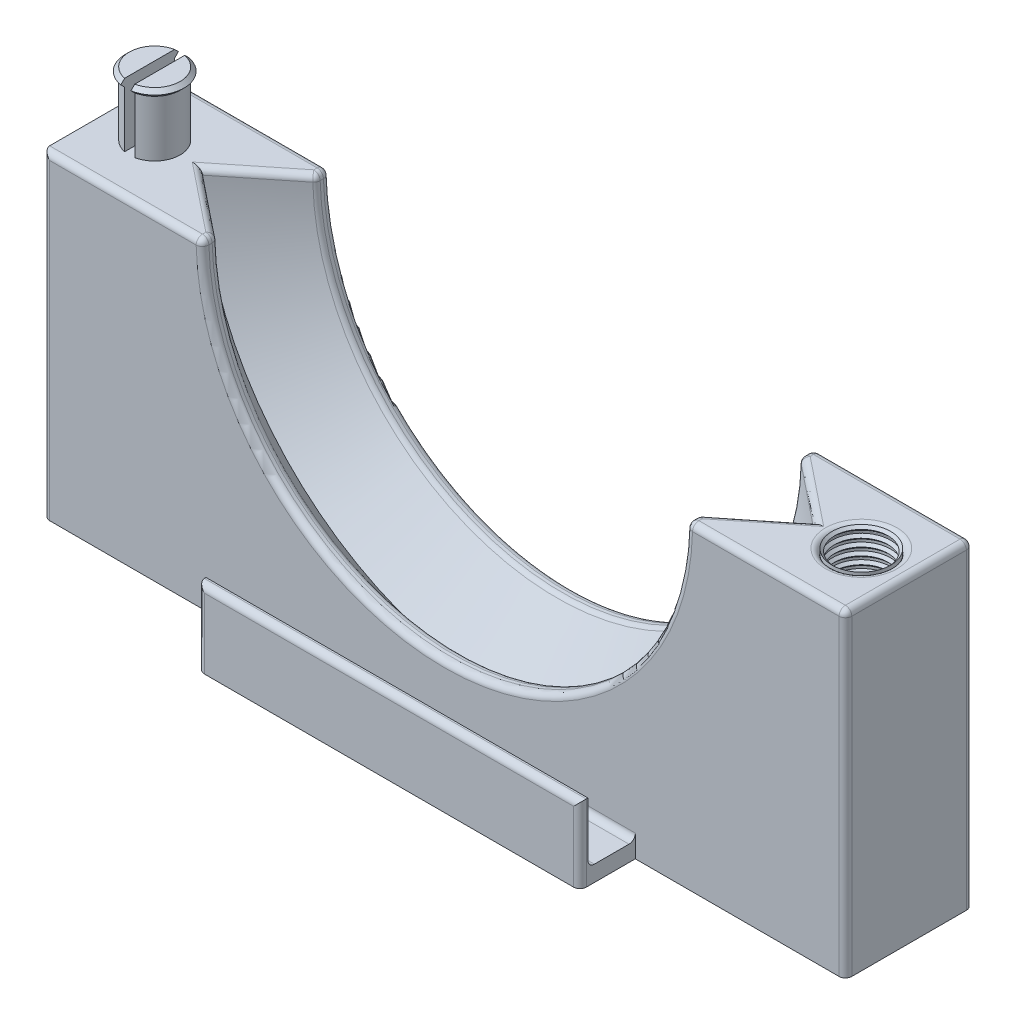
SolidWorks part; units mm, degrees
ref_plane "Front Plane" through (0, 0, 0) normal (0, 0, 1) x (1, 0, 0)
ref_plane "Top Plane" through (0, 0, 0) normal (0, 1, 0) x (1, 0, 0)
ref_plane "Right Plane" through (0, 0, 0) normal (1, 0, 0) x (0, 0, -1)
sketch "Sketch1" plane through (0, 0, 0) normal (0, 0, 1) x (1, 0, 0)
  line L0 (-40.005, 0) -> (40.005, 0)
  line L1 (40.005, 0) -> (40.005, 31.75)
  line L2 (40.005, 31.75) -> (24.13, 31.75)
  line L3 (-24.13, 31.75) -> (-40.005, 31.75)
  line L4 (-40.005, 31.75) -> (-40.005, 0)
  arc A0 (24.13, 31.75) -> (-24.13, 31.75) centre (0, 31.75) cw
  point P7 (0, 0)
  dimension "D2" = 24.13
  dimension "D1" = 31.75
  dimension "D3" = 15.875
extrude "Boss-Extrude1" add sketch "Sketch1" along normal blind 12.7
sketch "Sketch2" plane through (0, 31.75, 0) normal (0, 1, 0) x (1, 0, 0)
  line L0 (24.13, -11.43) -> (30.48, -6.35)
  line L2 (24.13, -12.7) -> (24.13, 0) construction
  line L3 (30.48, -6.35) -> (24.13, -1.27)
  line L4 (22.8654, -6.35) -> (40.005, -6.35) construction
  line L5 (24.13, -1.27) -> (24.13, -11.43)
  line L6 (40.005, -12.7) -> (40.005, 0) construction
  line L7 (0, 0) -> (0, -23.6383) construction
  dimension "D1" = 10.16
  dimension "D2" = 6.35
revolve "Cut-Revolve1" cut sketch "Sketch2" angle 360 about L7
sketch "Sketch6" plane through (0, 31.75, 0) normal (0, 1, 0) x (1, 0, 0)
  line L0 (30.48, -6.35) -> (40.005, -6.35) construction
  line L1 (40.005, -12.7) -> (40.005, 0) construction
  circle A0 centre (35.2425, -6.35) radius 2.921
  dimension "D1" = 5.842
extrude "Cut-Extrude2" cut sketch "Sketch6" against normal blind 9.525
sketch "Sketch11" plane through (0, 31.75, 0) normal (0, 1, 0) x (1, 0, 0)
  line L0 (30.48, -6.35) -> (40.005, -6.35) construction
  line L1 (40.005, -12.7) -> (40.005, 0) construction
ref_plane "Plane1" through (0, 0, 6.35) normal (0, 0, 1) x (1, 0, 0)
sketch "Sketch15" plane through (0, 0, 6.35) normal (0, 0, 1) x (1, 0, 0)
  line L0 (-37.7825, 31.75) -> (-37.7825, 37.338)
  line L1 (-24.13, 31.75) -> (-40.005, 31.75) construction
  line L2 (-37.7825, 37.338) -> (-38.1635, 37.719)
  line L3 (-38.1635, 37.719) -> (-37.7825, 38.1)
  line L4 (-37.7825, 38.1) -> (-35.2425, 38.1)
  line L5 (-35.2425, 38.1) -> (-35.2425, 31.75)
  line L6 (-35.2425, 31.75) -> (-37.7825, 31.75)
  line L7 (-40.005, 31.75) -> (-40.005, 0) construction
  line L8 (-37.7825, 38.1) -> (-37.7825, 37.338) construction
  line L9 (-30.48, 31.75) -> (-40.005, 31.75) construction
  dimension "D1" = 2.54
  dimension "D3" = 6.35
  dimension "D4" = 90
  dimension "D5" = 2.921
revolve "Revolve2" add sketch "Sketch15" angle 360 about L5
sketch "Sketch12" plane through (0, 0, 6.35) normal (0, 0, 1) x (1, 0, 0)
  line L0 (35.2425, 31.75) -> (35.2425, 26.6144) construction
  line L1 (30.48, 31.75) -> (40.005, 31.75) construction
  line L2 (32.3215, 30.48) -> (32.5755, 30.734)
  line L3 (32.3215, 31.242) -> (32.5755, 31.496)
  line L4 (32.5755, 31.496) -> (32.3215, 31.75)
  line L5 (32.3215, 31.75) -> (32.3215, 31.242)
  line L6 (35.2425, 31.75) -> (32.3215, 31.75) construction
  line L7 (32.5755, 30.734) -> (32.3215, 30.988)
  line L8 (32.3215, 30.988) -> (32.3215, 30.48)
  line L9 (32.3215, 29.718) -> (32.5755, 29.972)
  line L10 (32.5755, 29.972) -> (32.3215, 30.226)
  line L11 (32.3215, 30.226) -> (32.3215, 29.718)
  line L12 (32.3215, 28.956) -> (32.5755, 29.21)
  line L13 (32.5755, 29.21) -> (32.3215, 29.464)
  line L14 (32.3215, 29.464) -> (32.3215, 28.956)
  line L15 (32.3215, 28.194) -> (32.5755, 28.448)
  line L16 (32.5755, 28.448) -> (32.3215, 28.702)
  line L17 (32.3215, 28.702) -> (32.3215, 28.194)
  line L18 (32.3215, 27.432) -> (32.5755, 27.686)
  line L19 (32.5755, 27.686) -> (32.3215, 27.94)
  line L20 (32.3215, 27.94) -> (32.3215, 27.432)
  line L21 (32.3215, 26.67) -> (32.5755, 26.924)
  line L22 (32.5755, 26.924) -> (32.3215, 27.178)
  line L23 (32.3215, 27.178) -> (32.3215, 26.67)
  line L24 (32.3215, 25.908) -> (32.5755, 26.162)
  line L25 (32.5755, 26.162) -> (32.3215, 26.416)
  line L26 (32.3215, 26.416) -> (32.3215, 25.908)
  line L27 (32.3215, 25.146) -> (32.5755, 25.4)
  line L28 (32.5755, 25.4) -> (32.3215, 25.654)
  line L29 (32.3215, 25.654) -> (32.3215, 25.146)
  line L30 (32.3215, 24.384) -> (32.5755, 24.638)
  line L31 (32.5755, 24.638) -> (32.3215, 24.892)
  line L32 (32.3215, 24.892) -> (32.3215, 24.384)
  line L33 (32.3215, 23.622) -> (32.5755, 23.876)
  line L34 (32.5755, 23.876) -> (32.3215, 24.13)
  line L35 (32.3215, 24.13) -> (32.3215, 23.622)
  line L36 (32.3215, 22.86) -> (32.5755, 23.114)
  line L37 (32.5755, 23.114) -> (32.3215, 23.368)
  line L38 (32.3215, 23.368) -> (32.3215, 22.86)
  line L39 (32.3215, 22.098) -> (32.5755, 22.352)
  line L40 (32.5755, 22.352) -> (32.3215, 22.606)
  line L41 (32.3215, 22.606) -> (32.3215, 22.098)
  line L42 (32.3215, 21.336) -> (32.5755, 21.59)
  line L43 (32.5755, 21.59) -> (32.3215, 21.844)
  line L44 (32.3215, 21.844) -> (32.3215, 21.336)
  line L45 (32.3215, 20.574) -> (32.5755, 20.828)
  line L46 (32.5755, 20.828) -> (32.3215, 21.082)
  line L47 (32.3215, 21.082) -> (32.3215, 20.574)
  line L48 (32.3215, 19.812) -> (32.5755, 20.066)
  line L49 (32.5755, 20.066) -> (32.3215, 20.32)
  line L50 (32.3215, 20.32) -> (32.3215, 19.812)
  line L51 (32.3215, 19.05) -> (32.5755, 19.304)
  line L52 (32.5755, 19.304) -> (32.3215, 19.558)
  line L53 (32.3215, 19.558) -> (32.3215, 19.05)
  line L54 (32.3215, 18.288) -> (32.5755, 18.542)
  line L55 (32.5755, 18.542) -> (32.3215, 18.796)
  line L56 (32.3215, 18.796) -> (32.3215, 18.288)
  line L57 (32.3215, 17.526) -> (32.5755, 17.78)
  line L58 (32.5755, 17.78) -> (32.3215, 18.034)
  line L59 (32.3215, 18.034) -> (32.3215, 17.526)
  line L60 (32.3215, 16.764) -> (32.5755, 17.018)
  line L61 (32.5755, 17.018) -> (32.3215, 17.272)
  line L62 (32.3215, 17.272) -> (32.3215, 16.764)
  dimension "D1" = 2.921
  dimension "D2" = 0.508
  dimension "D3" = 90
  dimension "D4" = 20
revolve "Revolve1" add sketch "Sketch12" angle 360 about L0
sketch "Sketch16" plane through (0, 38.1, 0) normal (0, 1, 0) x (1, 0, 0)
  line L1 (-35.7505, -11.9418) -> (-34.7345, -11.9418)
  line L2 (-35.7505, -11.9418) -> (-35.7505, -0.7582)
  line L3 (-35.7505, -0.7582) -> (-34.7345, -0.7582)
  line L4 (-34.7345, -11.9418) -> (-34.7345, -0.7582)
  line L5 (-35.7505, -11.9418) -> (-34.7345, -0.7582) construction
  line L6 (-35.7505, -0.7582) -> (-34.7345, -11.9418) construction
  point P0 (-35.2425, -6.35)
  dimension "D1" = 1.016
extrude "Cut-Extrude3" cut sketch "Sketch16" against normal up to surface (6.35 mm away) up to face at (-35.2425, 31.75, 8.89)
sketch "Sketch17" plane through (0, 0, 12.7) normal (0, 0, 1) x (1, 0, 0)
  line L0 (-40.005, 0) -> (40.005, 0) construction
  line L1 (-19.05, 0) -> (19.05, 0)
  line L2 (-19.05, 0) -> (-19.05, 1.5875)
  line L3 (-19.05, 1.5875) -> (19.05, 1.5875)
  line L4 (19.05, 0) -> (19.05, 1.5875)
  line L5 (0, 1.5875) -> (0, 0) construction
  dimension "D1" = 38.1
  dimension "D2" = 1.5875
extrude "Boss-Extrude2" add sketch "Sketch17" along normal blind 4.7244
sketch "Sketch18" plane through (0, 0, 17.4244) normal (0, 0, 1) x (1, 0, 0)
  line L0 (19.05, 0) -> (19.05, 1.5875) construction
  line L1 (-19.05, 0) -> (19.05, 0)
  line L2 (-19.05, 0) -> (-19.05, 7.62)
  line L3 (-19.05, 7.62) -> (19.05, 7.62)
  line L4 (19.05, 0) -> (19.05, 7.62)
  dimension "D1" = 7.62
extrude "Boss-Extrude3" add sketch "Sketch18" along normal blind 0.8
fillet "Fillet1" radius 0.635 27 edges at (-24.13, 31.75, 0.635) (0, 7.62, 0) (0, 7.62, 1.27) (27.305, 31.75, 3.81) (24.13, 31.75, 0.635) (32.0675, 31.75, 0) (40.005, 31.75, 6.35) (32.0675, 31.75, 12.7) (27.305, 31.75, 8.89) (32.3215, 31.75, 6.35) (24.13, 31.75, 12.065) (0, 7.62, 12.7) (-24.13, 31.75, 12.065) (0, 7.62, 11.43) (19.05, 3.81, 18.2244) (0, 7.62, 18.2244) (-19.05, 3.81, 18.2244) (0, 1.5875, 12.7) (-32.0675, 31.75, 0) (-32.0675, 31.75, 12.7) (-40.005, 15.875, 0) (-40.005, 15.875, 12.7) (40.005, 15.875, 0) (40.005, 15.875, 12.7) (-27.305, 31.75, 3.81) (-27.305, 31.75, 8.89)
